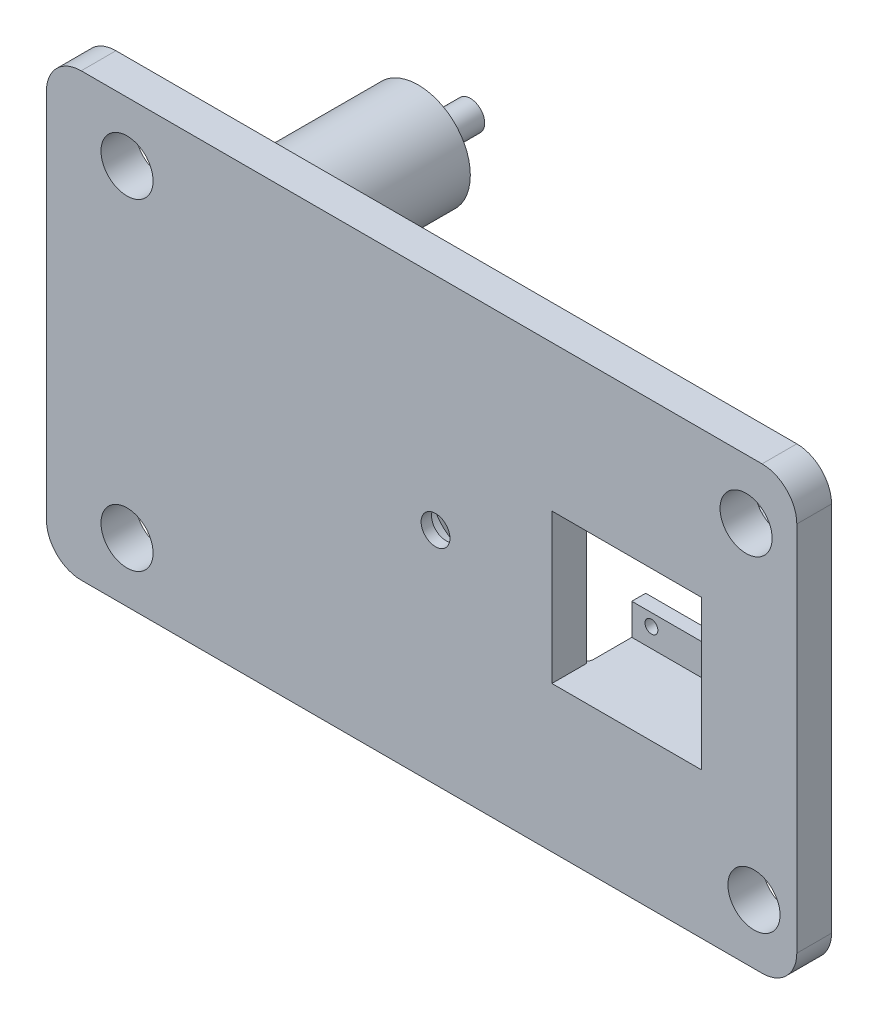
SolidWorks part; units mm, degrees
ref_plane "Front Plane" through (0, 0, 0) normal (0, 0, 1) x (1, 0, 0)
ref_plane "Top Plane" through (0, 0, 0) normal (0, 1, 0) x (1, 0, 0)
ref_plane "Right Plane" through (0, 0, 0) normal (1, 0, 0) x (0, 0, -1)
sketch "Sketch1" plane through (0, 0, 0) normal (0, 0, 1) x (1, 0, 0)
  line L1 (-108, 63.5) -> (108, 63.5)
  line L2 (-108, 63.5) -> (-108, -63.5)
  line L3 (-108, -63.5) -> (108, -63.5)
  line L4 (108, 63.5) -> (108, -63.5)
  line L5 (-108, 63.5) -> (108, -63.5) construction
  line L6 (-108, -63.5) -> (108, 63.5) construction
  point P0 (0, 0)
  dimension "D1" = 127
  dimension "D2" = 216
extrude "Boss-Extrude1" add sketch "Sketch1" along normal blind 10
fillet "Fillet1" radius 10 1 edges at (-108, 63.5, 5)
fillet "Fillet2" radius 10 3 edges at (-108, -63.5, 5) (108, 63.5, 5) (108, -63.5, 5)
sketch "Sketch9" plane through (0, 0, 0) normal (0, 0, -1) x (-1, 0, 0)
  line L0 (-98, 63.5) -> (98, 63.5) construction
  line L1 (-37.5, -21.5) -> (-80.5, -21.5)
  line L2 (-37.5, -21.5) -> (-37.5, 21.5)
  line L3 (-37.5, 21.5) -> (-80.5, 21.5)
  line L4 (-80.5, -21.5) -> (-80.5, 21.5)
  line L5 (-37.5, -21.5) -> (-80.5, 21.5) construction
  line L6 (-37.5, 21.5) -> (-80.5, -21.5) construction
  line L8 (108, 0) -> (-108, 0) construction
  line L9 (108, 53.5) -> (108, -53.5) construction
  line L10 (-108, -53.5) -> (-108, 53.5) construction
  circle A0 centre (-4, 0) radius 11.35
  point P2 (-59, 0)
  dimension "D6" = 22.7
  dimension "D1" = 27.5
  dimension "D2" = 55
  dimension "D3" = 43
  dimension "D4" = 43
  dimension "D5" = 63.5
extrude "Cut-Extrude4" cut sketch "Sketch9" against normal blind 7 contours A0
sketch "Sketch12" plane through (0, 0, 7) normal (0, 0, -1) x (-1, 0, 0)
  circle A0 centre (-4, 0) radius 4.15
  dimension "D1" = 8.3
extrude "Cut-Extrude5" cut sketch "Sketch12" against normal blind 7
extrude "Cut-Extrude6" cut sketch "Sketch9<4>" against normal through all contours L3 L4 L1 L2
sketch "Sketch9<4>" plane through (0, 0, 0) normal (0, 0, -1) x (-1, 0, 0) same geometry as "Sketch9"
sketch "Sketch13" plane through (0, 0, 0) normal (0, 0, -1) x (-1, 0, 0)
  line L1 (-37.5, -21.5) -> (-80.5, -21.5)
  line L2 (-37.5, -21.5) -> (-37.5, -25.5)
  line L3 (-37.5, -25.5) -> (-80.5, -25.5)
  line L4 (-80.5, -21.5) -> (-80.5, -25.5)
  dimension "D1" = 4
  dimension "D2" = 43
extrude "Boss-Extrude2" add sketch "Sketch13" along normal blind 17
ref_plane "Plane3" through (0, -21.5, 0) normal (0, 1, 0) x (1, 0, 0)
ref_plane "Plane4" through (0, 0, 0) normal (0, 0, -1) x (-1, 0, 0)
ref_plane "Plane6" through (80.5, 0, 0) normal (1, 0, 0) x (0, 0, -1)
sketch "Sketch16" plane through (80.5, 0, 0) normal (1, 0, 0) x (0, 0, -1)
  line L0 (17, -21.5) -> (0, -21.5) construction
  line L1 (17.0075, -21.5) -> (0.1109, -21.5)
  line L2 (17.0075, -21.5) -> (17.0075, -25.5)
  line L3 (17.0075, -25.5) -> (0.1109, -25.5)
  line L4 (0.1109, -21.5) -> (0.1109, -25.5)
  line L5 (17, -25.5) -> (0, -25.5) construction
fillet "Fillet4" radius 2 3 edges at (59, -25.5, 0) (37.5, -23.5, 0) (80.5, -23.5, 0)
sketch "Sketch17" plane through (0, -21.5, 0) normal (0, 1, 0) x (1, 0, 0)
  line L0 (80.5, 17.0075) -> (80.5, 0.1109) construction
  line L1 (37.5, 17) -> (80.5, 17)
  line L2 (37.5, 17) -> (37.5, 13)
  line L3 (37.5, 13) -> (80.5, 13)
  line L4 (80.5, 17) -> (80.5, 13)
  dimension "D1" = 4
extrude "Boss-Extrude5" add sketch "Sketch17" along normal blind 9
sketch "Sketch18" plane through (0, 0, 0) normal (0, 0, -1) x (-1, 0, 0)
  line L1 (-37.5, 21.5) -> (-80.5, 21.5)
  line L2 (-37.5, 21.5) -> (-37.5, 25.5)
  line L3 (-37.5, 25.5) -> (-80.5, 25.5)
  line L4 (-80.5, 21.5) -> (-80.5, 25.5)
  dimension "D1" = 43
  dimension "D2" = 4
extrude "Boss-Extrude6" add sketch "Sketch18" along normal blind 17
ref_plane "Plane7" through (0, 21.5, 0) normal (0, -1, 0) x (-1, 0, 0)
sketch "Sketch19" plane through (0, 21.5, 0) normal (0, -1, 0) x (-1, 0, 0)
  line L0 (-80.5, 17) -> (-80.5, 0) construction
  line L1 (-37.5, 17) -> (-80.5, 17)
  line L2 (-37.5, 17) -> (-37.5, 13)
  line L3 (-37.5, 13) -> (-80.5, 13)
  line L4 (-80.5, 17) -> (-80.5, 13)
  dimension "D1" = 4
extrude "Boss-Extrude7" add sketch "Sketch19" along normal blind 9
fillet "Fillet5" radius 2 3 edges at (37.5, 23.5, 0) (80.5, 23.5, 0) (59, 25.5, 0)
ref_plane "Plane8" through (0, 0, -17) normal (0, 0, -1) x (-1, 0, 0)
sketch "Sketch20" plane through (0, 0, -17) normal (0, 0, -1) x (-1, 0, 0)
  line L0 (-37.5, -25.5) -> (-37.5, -12.5) construction
  line L2 (-80.5, -21.5) -> (-37.5, -21.5)
  line L3 (-80.5, -12.5) -> (-80.5, -25.5) construction
  line L4 (-80.5, -12.5) -> (-37.5, -12.5) construction
  circle A0 centre (-43.15, -16) radius 1.85
  circle A1 centre (-74.85, -16) radius 1.85
  dimension "D3" = 5.5
  dimension "D4" = 3.7
  dimension "D5" = 5.65
  dimension "D6" = 3.7
  dimension "D1" = 5.65
  dimension "D2" = 9
extrude "Cut-Extrude7" cut sketch "Sketch20" against normal blind 9 contours A1 | A0
ref_plane "Plane9" through (0, 0, -17) normal (0, 0, -1) x (-1, 0, 0)
sketch "Sketch23" plane through (0, 0, -17) normal (0, 0, -1) x (-1, 0, 0)
  line L0 (-37.5, 21.5) -> (-80.5, 21.5)
  line L1 (-37.5, 12.5) -> (-37.5, 25.5) construction
  line L2 (-80.5, 25.5) -> (-80.5, 12.5) construction
  line L3 (-37.5, 12.5) -> (-80.5, 12.5) construction
  circle A0 centre (-43.15, 15.85) radius 1.85
  circle A1 centre (-74.85, 16) radius 1.85
  dimension "D4" = 3.7
  dimension "D5" = 3.7
  dimension "D6" = 5.65
  dimension "D7" = 5.65
  dimension "D1" = 9
  dimension "D2" = 5.5
  dimension "D3" = 5.65
extrude "Cut-Extrude8" cut sketch "Sketch23" against normal blind 9 contours A0 | A1
ref_plane "Plane10" through (0, 0, 0) normal (0, 0, -1) x (-1, 0, 0)
sketch "Sketch25" plane through (0, 0, 0) normal (0, 0, -1) x (-1, 0, 0)
  line L0 (5.8491, 5.5555) -> (-13.8858, -5.5762)
  line L1 (-4, -11.35) -> (-4, 11.35)
  line L2 (98, -63.5) -> (-98, -63.5) construction
  line L3 (-98, 63.5) -> (98, 63.5) construction
  circle A0 centre (5.8491, 5.5555) radius 0.0422
  circle A1 centre (-4, 0) radius 11.35 construction
  circle A2 centre (50.9816, -43.5) radius 15
  circle A3 centre (50.9816, 43.5) radius 15
  point P8 (-4.0184, -0.0104)
  dimension "D4" = 20
  dimension "D5" = 30
  dimension "D6" = 30
  dimension "D1" = 55
  dimension "D2" = 55
  dimension "D3" = 20
extrude "Boss-Extrude9" add sketch "Sketch25" along normal blind 40 contours A3 | A2
ref_plane "Plane11" through (0, 0, -40) normal (0, 0, -1) x (-1, 0, 0)
sketch "Sketch26" plane through (0, 0, -40) normal (0, 0, -1) x (-1, 0, 0)
  circle A0 centre (50.9816, -43.5) radius 4.15
  dimension "D1" = 8.3
extrude "Boss-Extrude10" add sketch "Sketch26" along normal blind 15
ref_plane "Plane12" through (0, 0, -40) normal (0, 0, -1) x (-1, 0, 0)
sketch "Sketch27" plane through (0, 0, -40) normal (0, 0, -1) x (-1, 0, 0)
  circle A0 centre (50.9816, 43.5) radius 4.15
  dimension "D1" = 8.3
extrude "Boss-Extrude11" add sketch "Sketch27" along normal blind 15
fillet "Fillet9" radius 2 1 edges at (-35.9816, -43.5, 0)
fillet "Fillet10" radius 2 1 edges at (-35.9816, 43.5, 0)
ref_plane "Plane13" through (0, 0, 10) normal (0, 0, 1) x (1, 0, 0)
sketch "Sketch28" plane through (0, 0, 10) normal (0, 0, 1) x (1, 0, 0)
  line L0 (98, 63.5) -> (-98, 63.5) construction
  line L3 (-98, -63.5) -> (98, -63.5) construction
  circle A0 centre (-84.8117, 46.37) radius 7.5
  circle A1 centre (-84.8117, -46.37) radius 7.5
  circle A2 centre (95.674, -46.3698) radius 7.5
  circle A3 centre (93.3991, 46.37) radius 7.5
  dimension "D2" = 15
  dimension "D3" = 17.13
  dimension "D4" = 15
  dimension "D5" = 17.13
  dimension "D6" = 15
  dimension "D7" = 15
  dimension "D1" = 17.13
extrude "Cut-Extrude9" cut sketch "Sketch28" against normal through all
